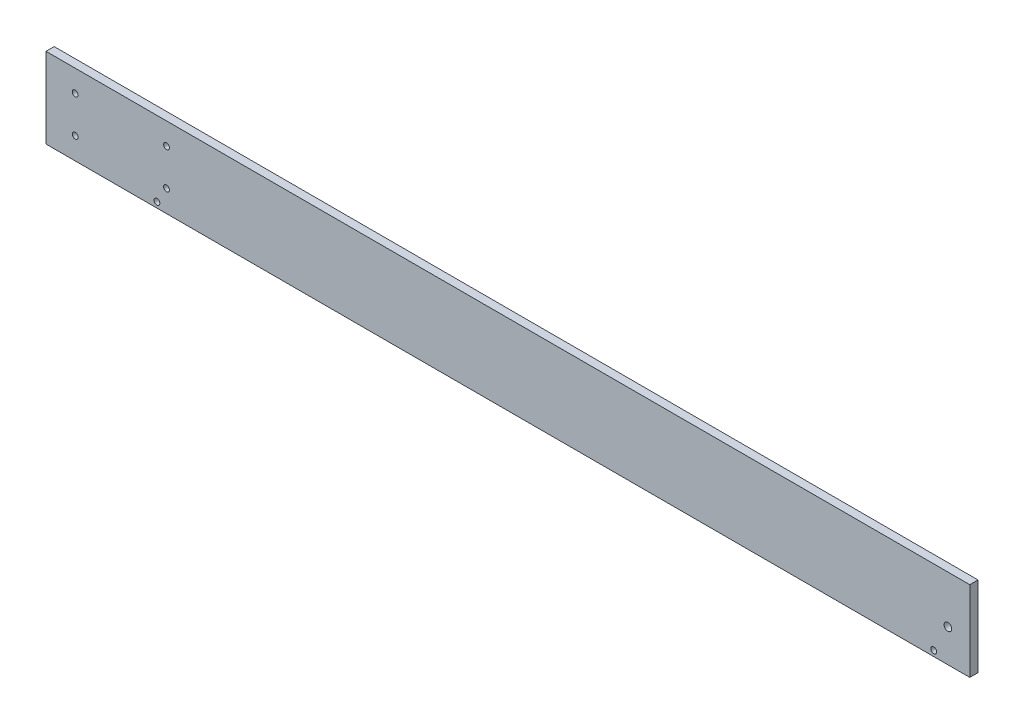
SolidWorks part; units mm, degrees
ref_plane "Front Plane" through (0, 0, 0) normal (0, 0, 1) x (1, 0, 0)
ref_plane "Top Plane" through (0, 0, 0) normal (0, 1, 0) x (1, 0, 0)
ref_plane "Right Plane" through (0, 0, 0) normal (1, 0, 0) x (0, 0, -1)
sketch "Sketch1" plane through (0, 0, 0) normal (0, 0, 1) x (1, 0, 0)
  line L0 (-253, 0) -> (-154.8681, 0) construction
  line L1 (-253, -22) -> (253, -22)
  line L2 (-253, -22) -> (-253, 22)
  line L3 (-253, 22) -> (253, 22)
  line L4 (253, -22) -> (253, 22)
  line L5 (-253, -22) -> (253, 22) construction
  line L6 (-253, 22) -> (253, -22) construction
  line L7 (-247, 6.6679) -> (-247, 39) construction
  circle A0 centre (241, -4) radius 2.1 construction
  circle A1 centre (241, -4) radius 2.1
  circle A2 centre (-237, 10) radius 1.6
  circle A3 centre (-187, 10) radius 1.6
  circle A6 centre (-187, -10) radius 1.6
  circle A9 centre (-237, -10) radius 1.6
  circle A10 centre (233.25, -19) radius 1.6 construction
  circle A11 centre (233.25, -19) radius 1.6
  circle A12 centre (-192.25, -19) radius 1.6 construction
  circle A13 centre (-192.25, -19) radius 1.6
  point P0 (0, 0)
  dimension "D3" = 3.2
  dimension "D1" = 506
  dimension "D2" = 44
  dimension "D4" = 10
  dimension "D5" = 10
  dimension "D6" = 2
  dimension "D7" = 2
extrude "Boss-Extrude1" add sketch "Sketch1" along normal blind 4.5
